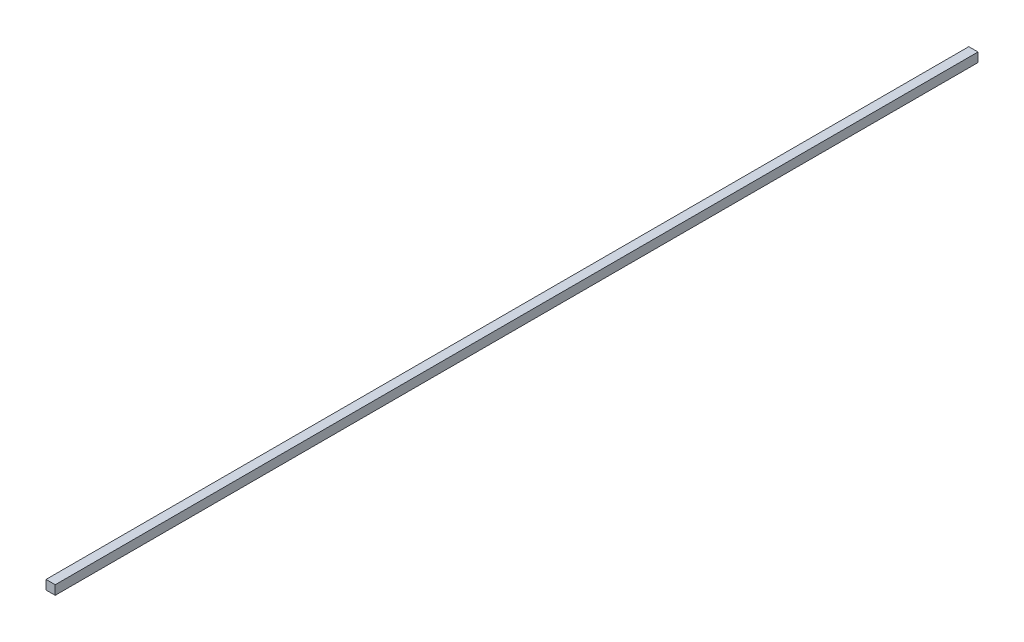
SolidWorks part; units mm, degrees
ref_plane "XY" through (0, 0, 0) normal (0, 0, 1) x (1, 0, 0)
ref_plane "XZ" through (0, 0, 0) normal (0, 1, 0) x (1, 0, 0)
ref_plane "YZ" through (0, 0, 0) normal (1, 0, 0) x (0, 0, -1)
ref_axis "X" through (-88.99, 0, 0) along (1, 0, 0)
ref_axis "Y" through (0, -55, 0) along (0, 1, 0)
ref_axis "Z" through (0, 0, 55) along (0, 0, -1)
sketch "Sketch1" plane through (0, 0, 0) normal (0, 0, 1) x (1, 0, 0)
  line L1 (-3.8, -3.8) -> (3.8, -3.8)
  line L2 (-3.8, -3.8) -> (-3.8, 3.8)
  line L3 (-3.8, 3.8) -> (3.8, 3.8)
  line L4 (3.8, -3.8) -> (3.8, 3.8)
  line L5 (-3.8, -3.8) -> (3.8, 3.8) construction
  line L6 (-3.8, 3.8) -> (3.8, -3.8) construction
  point P0 (0, 0)
  dimension "D1" = 7.6
extrude "Boss-Extrude1" add sketch "Sketch1" along normal blind 762
